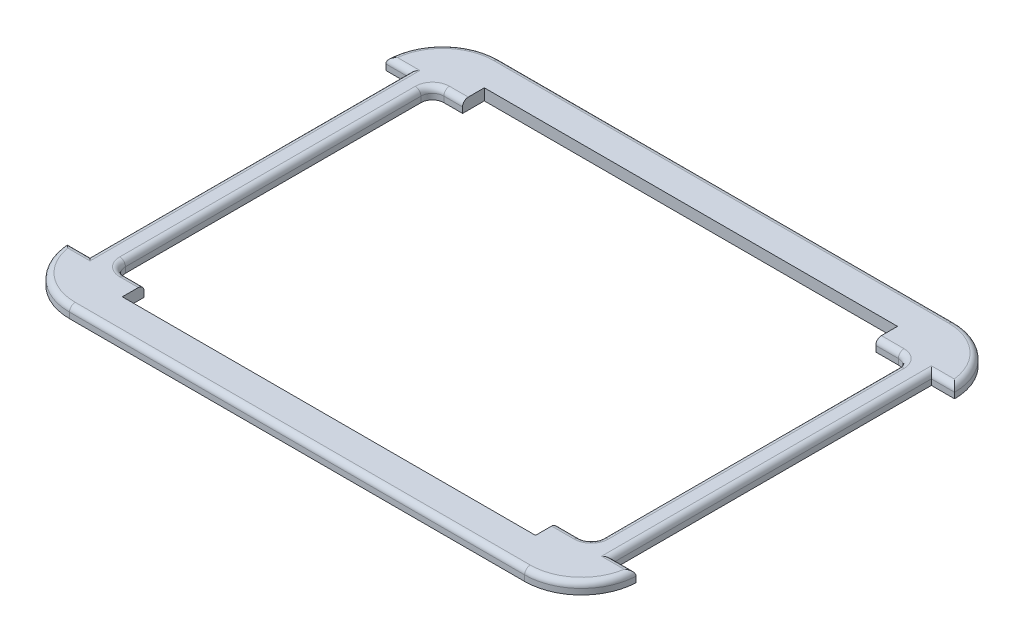
SolidWorks part; units mm, degrees
material "ABS"
ref_plane "Front Plane" through (0, 0, 0) normal (0, 0, 1) x (1, 0, 0)
ref_plane "Top Plane" through (0, 0, 0) normal (0, 1, 0) x (1, 0, 0)
ref_plane "Right Plane" through (0, 0, 0) normal (1, 0, 0) x (0, 0, -1)
sketch "Sketch1" plane through (0, 0, 0) normal (0, 1, 0) x (1, 0, 0)
  line L0 (0, 0) -> (0, 20.4297) construction
  line L1 (-25, -18.9) -> (25, -18.9)
  line L2 (-25, -18.9) -> (-25, -14.1)
  line L3 (-25, 18.9) -> (25, 18.9)
  line L4 (25, -18.9) -> (25, -14.1)
  line L5 (-25, -18.9) -> (25, 18.9) construction
  line L6 (-25, 18.9) -> (25, -18.9) construction
  line L7 (-18.351, 15.9114) -> (17.971, 15.9114)
  line L11 (0, 0) -> (30.9101, 0) construction
  line L12 (-21, -12.9883) -> (-21, 12.9883)
  line L13 (20.96, 13) -> (20.96, -13)
  line L14 (-18.351, -15.9114) -> (17.971, -15.9114)
  line L15 (25, -14.1) -> (22.96, -14.1)
  line L16 (25, 13.9) -> (22.96, 13.9)
  line L18 (25, 13.9) -> (25, 18.9)
  line L19 (-23, -14.1) -> (-25, -14.1)
  line L20 (-23, 13.9) -> (-25, 13.9)
  line L21 (-23, -14.1) -> (-23, 13.9)
  line L22 (-25, 13.9) -> (-25, 18.9)
  line L23 (22.96, -14.1) -> (22.96, 13.9)
  line L24 (19.96, 14) -> (17.971, 14)
  line L25 (19.96, -14) -> (17.971, -14)
  line L27 (17.971, -14) -> (17.971, -15.9114)
  line L28 (17.971, 14) -> (17.971, 15.9114)
  line L29 (-18.351, -15.9114) -> (-18.351, -14)
  line L31 (-18.351, -14) -> (-20, -14)
  line L32 (-18.351, 15.9114) -> (-18.351, 14)
  line L33 (-18.351, 14) -> (-20, 14)
  arc A5 (19.96, -14) -> (20.96, -13) centre (19.96, -13) ccw
  arc A6 (19.96, 14) -> (20.96, 13) centre (19.96, 13) cw
  arc A8 (-20, -14) -> (-21, -12.9883) centre (-20, -12.9999) cw
  arc A10 (-21, 12.9883) -> (-20, 14) centre (-20, 12.9999) cw
  point P0 (0, 0)
  point P32 (0, 0)
  point P33 (0, 0)
  point P36 (0, 0)
  point P37 (0, 0)
  point P38 (0, 0)
  point P39 (0, 0)
  point P40 (0, 0)
  point P41 (0, 0)
  point P43 (0, 0)
  point P44 (0, 0)
  point P45 (0, 0)
  point P48 (0, 0)
  point P49 (0, 0)
  point P51 (0, 0)
  point P52 (0, 0)
  point P54 (0, 0)
  point P55 (0, 0)
  point P56 (0, 0)
  point P57 (0, 0)
  point P58 (0, 0)
  point P59 (0, 0)
  point P60 (0, 0)
  point P61 (0, 0)
  point P62 (0, 0)
  point P63 (0, 0)
  point P64 (0, 0)
  point P65 (0, 0)
extrude "Boss-Extrude1" add sketch "Sketch1" along normal blind 1
fillet "Fillet1" radius 5 4 edges at (25, 0.5, 18.9) (-25, 0.5, 18.9) (-25, 0.5, -18.9) (25, 0.5, -18.9)
fillet "Fillet2" radius 0.5 22 edges at (-23.4681, 1, 17.5056) (0, 1, -18.9) (23.4681, 1, 17.5056) (0, 1, 18.9) (-23.5355, 1, -17.4355) (-24, 1, 14.1) (-23, 1, 0.1) (-24, 1, -13.9) (23.5355, 1, -17.4355) (23.98, 1, -13.9) (22.96, 1, 0.1) (23.98, 1, 14.1) (-21, 1, 0) (20.96, 1, 0) (-19.1755, 1, -14) (-20.7113, 1, -13.7029) (-19.1755, 1, 14) (-20.7113, 1, 13.7029) (18.9655, 1, 14) (20.6671, 1, 13.7071) (18.9655, 1, -14) (20.6671, 1, -13.7071)
